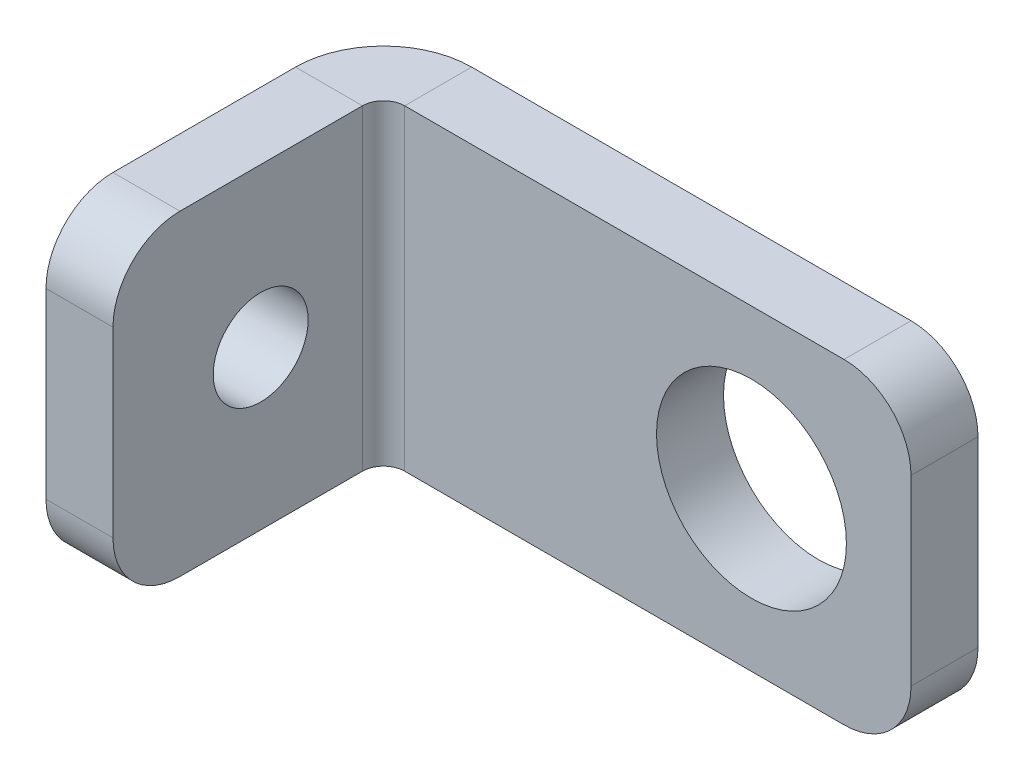
SolidWorks part; units mm, degrees
note: The reader was unsure of these and kept them because the rebuilt part matched: flange length of "Edge-Flange1".
material "3003-H14"
ref_plane "X-Y Datum" through (0, 0, 0) normal (0, 0, 1) x (1, 0, 0)
ref_plane "X-Z Datum" through (0, 0, 0) normal (0, 1, 0) x (1, 0, 0)
ref_plane "Y-Z Datum" through (0, 0, 0) normal (1, 0, 0) x (0, 0, -1)
sketch "Sketch1" plane through (0, 0, 0) normal (0, 0, 1) x (1, 0, 0)
  line L1 (-12.5, -7.5) -> (12.5, -7.5)
  line L2 (-12.5, -7.5) -> (-12.5, 7.5)
  line L3 (-12.5, 7.5) -> (12.5, 7.5)
  line L4 (12.5, -7.5) -> (12.5, 7.5)
  line L5 (-12.5, -7.5) -> (12.5, 7.5) construction
  line L6 (-12.5, 7.5) -> (12.5, -7.5) construction
  point P0 (0, 0)
  dimension "D1" = 15
  dimension "D2" = 25
base flange "Base-Flange1" sketch "Sketch1" thickness 3.175 reverse thickness direction yes parameters "D1"=10
edge flange "Edge-Flange1" sketch "Sketch8" flange angle 90 flange length 16 flange position material outside bend radius 1 thickness 3.175 relief rectangular parameters "D6"=10
sketch "Sketch8" plane through (-12.5, 0, 3.175) normal (1, 0, 0) x (0, 1, 0)
  line L2 (-7.5, 0) -> (-7.5, 12.825)
  line L3 (-7.5, 12.825) -> (7.5, 12.825)
  line L4 (7.5, 12.825) -> (7.5, 0)
  line L5 (7.5, 0) -> (-7.5, 0) construction
  line L6 (7.5, 0) -> (-7.5, 0)
bend "EdgeBend1" bend radius 1 bend angle 90 parameters "D5"=1
sketch "Sketch10" plane through (-12.5, 0, 0) normal (1, 0, 0) x (0, 0, -1)
  point P0 (-9, 0)
sketch "Sketch16" plane through (0, 0, 3.175) normal (0, 0, 1) x (1, 0, 0)
  point P0 (4.9369, 0)
hole_wizard "M8 Clearance Hole2" positions "Sketch16" profile "Sketch17" hole size "M8" standard "ANSI Metric" end condition through all
sketch "Sketch17" plane through (4.9369, 0, 3.175) normal (1, 0, 0) x (0, -1, 0)
  line L0 (0, 0) -> (0, 3.175)
  line L1 (0, 3.175) -> (4.5, 3.175)
  line L2 (4.5, 3.175) -> (4.5, 0)
  line L5 (4.5, 0) -> (0, 0)
  line L11 (0, -6.35) -> (0, 107.95) construction
  dimension "Thru Hole Dia." = 9
  dimension "Thru Hole Depth" = 3.175
fillet "Fillet1" radius 3.175 4 edges at (-14.0875, -7.5, 16) (-14.0875, 7.5, 16) (12.5, 7.5, 1.5875) (12.5, -7.5, 1.5875)
hole_wizard "M4 Clearance Hole2" positions "Sketch22" profile "Sketch21" hole size "M4" standard "ANSI Metric" end condition through all
sketch "Sketch22" plane through (-12.5, 0, 0) normal (1, 0, 0) x (0, 0, -1)
  point P0 (-9, 0)
sketch "Sketch21" plane through (-12.5, 0, 9) normal (0, 1, 0) x (0, 0, -1)
  line L0 (0, 0) -> (0, 3.175)
  line L1 (0, 3.175) -> (2.25, 3.175)
  line L2 (2.25, 3.175) -> (2.25, 0)
  line L5 (2.25, 0) -> (0, 0)
  line L11 (0, -6.35) -> (0, 107.95) construction
  dimension "Thru Hole Dia." = 4.5
  dimension "Thru Hole Depth" = 3.175
sketch "Bend-Lines1" [suppressed] plane through (0, 0, 0) normal (0, 1, 0) x (1, 0, 0)
sketch "Bounding-Box1" [suppressed] plane through (0, 0, 0) normal (0, 1, 0) x (1, 0, 0)
sheet metal parameters "Sheet-Metal1" thickness 3.175 parameters "D1"=10
flat pattern "Flat-Pattern1" [suppressed]
sketch "Bend-Lines2" plane through (0, 0, 0) normal (0, 1, 0) x (1, 0, 0)
sketch3d "Bounding-Box2" [suppressed]
  line L0 (-8.25, -7.5, 0) -> (8.25, -7.5, 0) construction
  line L1 (-8.25, 7.5, 0) -> (8.25, 7.5, 0) construction
  line L2 (-8.25, -7.5, 0) -> (-8.25, 7.5, 0) construction
  line L3 (8.25, -7.5, 0) -> (8.25, 7.5, 0) construction
sheet metal parameters "Sheet-Metal2" thickness 3.175 parameters "D1"=10
flat pattern "Flat-Pattern1"
sketch "Bend-Lines2" plane through (0, 0, 0) normal (0, 0, -1) x (-1, 0, 0)
  line L0 (9.2822, -7.5) -> (9.2822, 7.5) construction
  line L1 (9.2822, -7.5) -> (9.2822, 7.5) construction
sketch3d "Bounding-Box2" [suppressed]
  line L0 (27.1394, -7.5, 0) -> (-8.25, -7.5, 0) construction
  line L1 (27.1394, 7.5, 0) -> (-8.25, 7.5, 0) construction
  line L2 (27.1394, -7.5, 0) -> (27.1394, 7.5, 0) construction
  line L3 (-8.25, -7.5, 0) -> (-8.25, 7.5, 0) construction
bend of the flat pattern "Flatten-<EdgeBend1>1"
sheet metal parameters "Sheet-Metal7" thickness 3.175 parameters "D1"=10
flat pattern "Flat-Pattern1" [suppressed]
sketch "Bend-Lines2" plane through (0, 0, 0) normal (0, 0, -1) x (-1, 0, 0)
  line L0 (13.5322, -10) -> (13.5322, 10) construction
  line L1 (13.5322, -10) -> (13.5322, 10) construction
sketch3d "Bounding-Box2" [suppressed]
  line L0 (29.3894, -10, 0) -> (-12.5, -10, 0) construction
  line L1 (29.3894, 10, 0) -> (-12.5, 10, 0) construction
  line L2 (29.3894, -10, 0) -> (29.3894, 10, 0) construction
  line L3 (-12.5, -10, 0) -> (-12.5, 10, 0) construction
bend of the flat pattern "Flatten-<EdgeBend1>1"
sketch "Sketch10-1" plane through (-11.3894, 0, 3.175) normal (0, 0, 1) x (1, 0, 0)
  point P0 (-11, 0)
sheet metal parameters "Sheet-Metal8" thickness 3.175 parameters "D1"=10
flat pattern "Flat-Pattern1" [suppressed]
sketch "Bend-Lines2" plane through (0, 0, 0) normal (0, 0, -1) x (-1, 0, 0)
  line L0 (13.5322, -7.5) -> (13.5322, 7.5) construction
  line L1 (13.5322, -7.5) -> (13.5322, 7.5) construction
sketch3d "Bounding-Box2" [suppressed]
  line L0 (27.3894, -7.5, 0) -> (-12.5, -7.5, 0) construction
  line L1 (27.3894, 7.5, 0) -> (-12.5, 7.5, 0) construction
  line L2 (27.3894, -7.5, 0) -> (27.3894, 7.5, 0) construction
  line L3 (-12.5, -7.5, 0) -> (-12.5, 7.5, 0) construction
bend of the flat pattern "Flatten-<EdgeBend1>1"
sketch "Sketch10-1" plane through (-11.3894, 0, 3.175) normal (0, 0, 1) x (1, 0, 0)
  point P0 (-9, 0)
